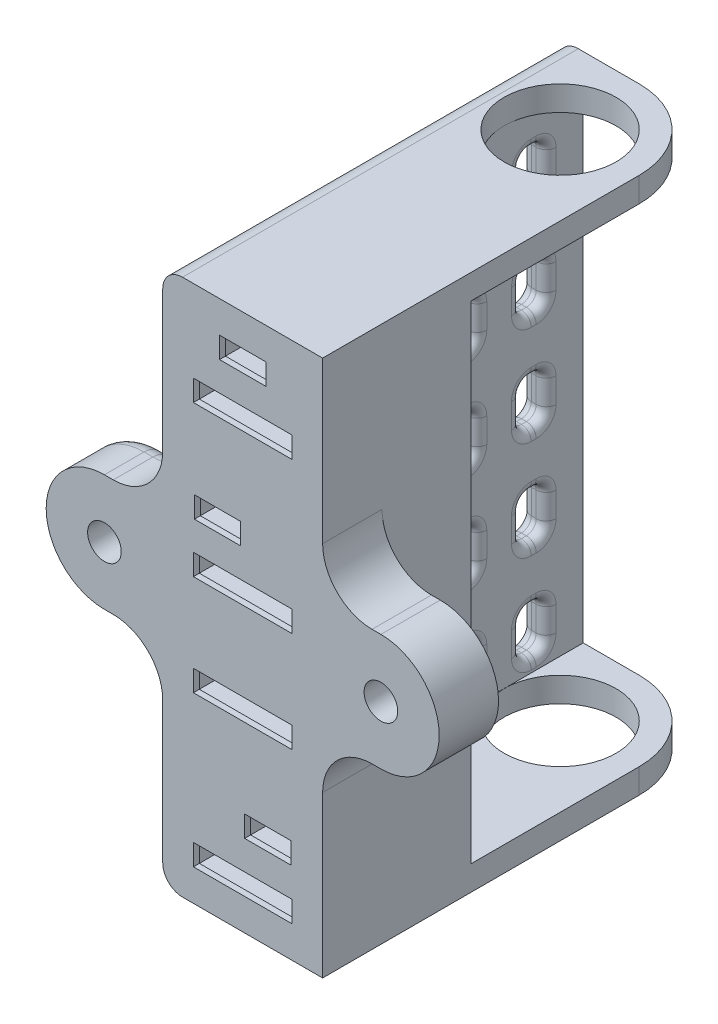
SolidWorks part; units mm, degrees
ref_plane "Plan de face" through (0, 0, 0) normal (0, 0, 1) x (1, 0, 0)
ref_plane "Plan de dessus" through (0, 0, 0) normal (0, 1, 0) x (1, 0, 0)
ref_plane "Plan de droite" through (0, 0, 0) normal (1, 0, 0) x (0, 0, -1)
sketch "Esquisse1" plane through (0, 0, 0) normal (0, 0, 1) x (1, 0, 0)
  line L44 (-8.08, 27.13) -> (8.08, 27.13)
  line L45 (-8.08, 27.13) -> (-8.08, -27.13)
  line L46 (-8.08, -27.13) -> (8.08, -27.13)
  line L47 (8.08, 27.13) -> (8.08, -27.13)
  line L48 (-8.08, 27.13) -> (8.08, -27.13) construction
  line L49 (-8.08, -27.13) -> (8.08, 27.13) construction
  point P1 (0, 0)
  dimension "D1" = 16.16
  dimension "D2" = 54.26
extrude "Boss.-Extru.1" add sketch "Esquisse1" along normal blind 15
sketch "Esquisse2" plane through (0, 0, 0) normal (0, 0, -1) x (-1, 0, 0)
  line L0 (8.08, -27.13) -> (-8.08, -27.13) construction
  line L1 (-2.54, 21.59) -> (2.54, 21.59) construction
  line L2 (-2.54, 21.59) -> (-2.54, 24.13) construction
  line L3 (-2.54, 24.13) -> (2.54, 24.13) construction
  line L4 (2.54, 21.59) -> (2.54, 24.13) construction
  line L5 (-2.54, 21.59) -> (2.54, 24.13) construction
  line L6 (-2.54, 24.13) -> (2.54, 21.59) construction
  line L7 (-5.08, 19.05) -> (5.08, 19.05) construction
  line L8 (-5.08, 19.05) -> (-5.08, 16.51) construction
  line L9 (-5.08, 16.51) -> (5.08, 16.51) construction
  line L10 (5.08, 19.05) -> (5.08, 16.51) construction
  line L11 (-5.08, 19.05) -> (5.08, 16.51) construction
  line L12 (-5.08, 16.51) -> (5.08, 19.05) construction
  line L13 (0, 24.13) -> (0, -24.13) construction
  line L14 (5.08, 6.35) -> (0, 6.35) construction
  line L15 (5.08, 6.35) -> (5.08, 8.89) construction
  line L16 (5.08, 8.89) -> (0, 8.89) construction
  line L17 (0, 6.35) -> (0, 8.89) construction
  line L18 (5.08, 6.35) -> (0, 8.89) construction
  line L19 (5.08, 8.89) -> (0, 6.35) construction
  line L21 (2.64, 24.23) -> (-2.64, 24.23)
  line L22 (5.08, 1.27) -> (-5.08, 1.27) construction
  line L23 (5.08, 1.27) -> (5.08, 3.81) construction
  line L24 (5.08, 3.81) -> (-5.08, 3.81) construction
  line L25 (-5.08, 1.27) -> (-5.08, 3.81) construction
  line L26 (5.08, 1.27) -> (-5.08, 3.81) construction
  line L27 (5.08, 3.81) -> (-5.08, 1.27) construction
  line L28 (2.64, 24.23) -> (2.64, 21.49)
  line L29 (-5.08, -8.89) -> (5.08, -8.89) construction
  line L30 (-5.08, -8.89) -> (-5.08, -6.35) construction
  line L31 (-5.08, -6.35) -> (5.08, -6.35) construction
  line L32 (5.08, -8.89) -> (5.08, -6.35) construction
  line L33 (-5.08, -8.89) -> (5.08, -6.35) construction
  line L34 (-5.08, -6.35) -> (5.08, -8.89) construction
  line L35 (2.64, 21.49) -> (-2.64, 21.49)
  line L36 (0, -16.51) -> (-5.08, -16.51) construction
  line L37 (0, -16.51) -> (0, -19.05) construction
  line L38 (0, -19.05) -> (-5.08, -19.05) construction
  line L39 (-5.08, -16.51) -> (-5.08, -19.05) construction
  line L40 (0, -16.51) -> (-5.08, -19.05) construction
  line L41 (0, -19.05) -> (-5.08, -16.51) construction
  line L42 (-2.64, 24.23) -> (-2.64, 21.49)
  line L43 (2.64, 24.23) -> (-2.64, 21.49) construction
  line L44 (5.08, -24.13) -> (-5.08, -24.13) construction
  line L45 (5.08, -24.13) -> (5.08, -21.59) construction
  line L46 (5.08, -21.59) -> (-5.08, -21.59) construction
  line L47 (-5.08, -24.13) -> (-5.08, -21.59) construction
  line L48 (5.08, -24.13) -> (-5.08, -21.59) construction
  line L49 (5.08, -21.59) -> (-5.08, -24.13) construction
  line L50 (2.64, 21.49) -> (-2.64, 24.23) construction
  line L51 (5.28, 19.15) -> (-5.28, 19.15)
  line L52 (5.28, 19.15) -> (5.28, 16.41)
  line L53 (5.28, 16.41) -> (-5.28, 16.41)
  line L54 (-5.28, 19.15) -> (-5.28, 16.41)
  line L55 (5.28, 19.15) -> (-5.28, 16.41) construction
  line L56 (5.28, 16.41) -> (-5.28, 19.15) construction
  line L57 (5.18, 8.99) -> (-0.1, 8.99)
  line L58 (5.18, 8.99) -> (5.18, 6.25)
  line L59 (5.18, 6.25) -> (-0.1, 6.25)
  line L60 (-0.1, 8.99) -> (-0.1, 6.25)
  line L61 (5.18, 8.99) -> (-0.1, 6.25) construction
  line L62 (5.18, 6.25) -> (-0.1, 8.99) construction
  line L63 (5.28, 3.91) -> (-5.28, 3.91)
  line L64 (5.28, 3.91) -> (5.28, 1.17)
  line L65 (5.28, 1.17) -> (-5.28, 1.17)
  line L66 (-5.28, 3.91) -> (-5.28, 1.17)
  line L67 (5.28, 3.91) -> (-5.28, 1.17) construction
  line L68 (5.28, 1.17) -> (-5.28, 3.91) construction
  line L69 (5.28, -6.25) -> (-5.28, -6.25)
  line L70 (5.28, -6.25) -> (5.28, -8.99)
  line L71 (5.28, -8.99) -> (-5.28, -8.99)
  line L72 (-5.28, -6.25) -> (-5.28, -8.99)
  line L73 (5.28, -6.25) -> (-5.28, -8.99) construction
  line L74 (5.28, -8.99) -> (-5.28, -6.25) construction
  line L75 (0.1, -16.41) -> (-5.18, -16.41)
  line L76 (0.1, -16.41) -> (0.1, -19.15)
  line L77 (0.1, -19.15) -> (-5.18, -19.15)
  line L78 (-5.18, -16.41) -> (-5.18, -19.15)
  line L79 (0.1, -16.41) -> (-5.18, -19.15) construction
  line L80 (0.1, -19.15) -> (-5.18, -16.41) construction
  line L81 (5.28, -21.49) -> (-5.28, -21.49)
  line L82 (5.28, -21.49) -> (5.28, -24.23)
  line L83 (5.28, -24.23) -> (-5.28, -24.23)
  line L84 (-5.28, -21.49) -> (-5.28, -24.23)
  line L85 (5.28, -21.49) -> (-5.28, -24.23) construction
  line L86 (5.28, -24.23) -> (-5.28, -21.49) construction
  point P4 (0, 22.86)
  point P5 (0, -24.13)
  point P11 (0, 17.78)
  point P12 (0, 17.78)
  point P14 (0, -27.13)
  point P19 (2.54, 7.62)
  point P20 (0, 0)
  point P24 (0, 22.86)
  point P29 (0, 2.54)
  point P37 (0, -7.62)
  point P45 (-2.54, -17.78)
  point P47 (2.54, 7.62)
  point P54 (0, -22.86)
  point P57 (0, 2.54)
  point P62 (0, -7.62)
  point P68 (-2.54, -17.78)
  point P73 (0, -22.86)
  dimension "D1" = 5.08
  dimension "D2" = 5.08
  dimension "D3" = 5.08
  dimension "D4" = 10.16
  dimension "D5" = 10.16
  dimension "D6" = 10.16
  dimension "D7" = 2.54
  dimension "D8" = 10.16
  dimension "D9" = 5.08
  dimension "D10" = 0.2
  dimension "D11" = 0.1
  dimension "D12" = 0.1
extrude "Enlèv. mat.-Extru.1" cut sketch "Esquisse2" against normal through all
sketch "Esquisse4" plane through (0, 0, 15) normal (0, 0, 1) x (1, 0, 0)
  line L0 (-4.98, -21.79) -> (-4.98, -23.93)
  line L1 (-4.98, -23.93) -> (4.98, -23.93)
  line L2 (4.98, -23.93) -> (4.98, -21.79)
  line L3 (4.98, -21.79) -> (-4.98, -21.79)
  line L4 (5.28, 16.41) -> (5.28, 19.15)
  line L5 (-5.28, 16.41) -> (5.28, 16.41)
  line L6 (-5.28, 19.15) -> (-5.28, 16.41)
  line L7 (5.28, 19.15) -> (-5.28, 19.15)
  line L8 (5.28, 16.41) -> (5.28, 19.15)
  line L9 (-5.28, 16.41) -> (5.28, 16.41)
  line L10 (-5.28, 19.15) -> (-5.28, 16.41)
  line L11 (5.28, 19.15) -> (-5.28, 19.15)
  line L12 (2.64, 21.49) -> (2.64, 24.23)
  line L13 (-2.64, 21.49) -> (2.64, 21.49)
  line L14 (-2.64, 24.23) -> (-2.64, 21.49)
  line L15 (2.64, 24.23) -> (-2.64, 24.23)
  line L16 (2.64, 21.49) -> (2.64, 24.23)
  line L17 (-2.64, 21.49) -> (2.64, 21.49)
  line L18 (-2.64, 24.23) -> (-2.64, 21.49)
  line L19 (2.64, 24.23) -> (-2.64, 24.23)
  line L20 (0.1, 6.25) -> (0.1, 8.99)
  line L21 (-5.18, 6.25) -> (0.1, 6.25)
  line L22 (-5.18, 8.99) -> (-5.18, 6.25)
  line L23 (0.1, 8.99) -> (-5.18, 8.99)
  line L24 (0.1, 6.25) -> (0.1, 8.99)
  line L25 (-5.18, 6.25) -> (0.1, 6.25)
  line L26 (-5.18, 8.99) -> (-5.18, 6.25)
  line L27 (0.1, 8.99) -> (-5.18, 8.99)
  line L28 (5.28, 1.17) -> (5.28, 3.91)
  line L29 (-5.28, 1.17) -> (5.28, 1.17)
  line L30 (-5.28, 3.91) -> (-5.28, 1.17)
  line L31 (5.28, 3.91) -> (-5.28, 3.91)
  line L32 (5.28, 1.17) -> (5.28, 3.91)
  line L33 (-5.28, 1.17) -> (5.28, 1.17)
  line L34 (-5.28, 3.91) -> (-5.28, 1.17)
  line L35 (5.28, 3.91) -> (-5.28, 3.91)
  line L36 (5.28, -8.99) -> (5.28, -6.25)
  line L37 (-5.28, -8.99) -> (5.28, -8.99)
  line L38 (-5.28, -6.25) -> (-5.28, -8.99)
  line L39 (5.28, -6.25) -> (-5.28, -6.25)
  line L40 (5.28, -8.99) -> (5.28, -6.25)
  line L41 (-5.28, -8.99) -> (5.28, -8.99)
  line L42 (-5.28, -6.25) -> (-5.28, -8.99)
  line L43 (5.28, -6.25) -> (-5.28, -6.25)
  line L44 (5.18, -19.15) -> (5.18, -16.41)
  line L45 (-0.1, -19.15) -> (5.18, -19.15)
  line L46 (-0.1, -16.41) -> (-0.1, -19.15)
  line L47 (5.18, -16.41) -> (-0.1, -16.41)
  line L48 (5.18, -19.15) -> (5.18, -16.41)
  line L49 (-0.1, -19.15) -> (5.18, -19.15)
  line L50 (-0.1, -16.41) -> (-0.1, -19.15)
  line L51 (5.18, -16.41) -> (-0.1, -16.41)
  line L52 (5.28, -24.23) -> (5.28, -21.49)
  line L53 (-5.28, -24.23) -> (5.28, -24.23)
  line L54 (-5.28, -21.49) -> (-5.28, -24.23)
  line L55 (5.28, -21.49) -> (-5.28, -21.49)
  line L56 (5.28, -24.23) -> (5.28, -21.49)
  line L57 (-5.28, -24.23) -> (5.28, -24.23)
  line L58 (-5.28, -21.49) -> (-5.28, -24.23)
  line L59 (5.28, -21.49) -> (-5.28, -21.49)
  line L60 (0.2, -16.71) -> (0.2, -18.85)
  line L61 (0.2, -18.85) -> (4.88, -18.85)
  line L62 (4.88, -18.85) -> (4.88, -16.71)
  line L63 (4.88, -16.71) -> (0.2, -16.71)
  line L64 (-4.98, -6.55) -> (-4.98, -8.69)
  line L65 (-4.98, -8.69) -> (4.98, -8.69)
  line L66 (4.98, -8.69) -> (4.98, -6.55)
  line L67 (4.98, -6.55) -> (-4.98, -6.55)
  line L68 (-4.98, 3.61) -> (-4.98, 1.47)
  line L69 (-4.98, 1.47) -> (4.98, 1.47)
  line L70 (4.98, 1.47) -> (4.98, 3.61)
  line L71 (4.98, 3.61) -> (-4.98, 3.61)
  line L72 (-4.88, 8.69) -> (-4.88, 6.55)
  line L73 (-4.88, 6.55) -> (-0.2, 6.55)
  line L74 (-0.2, 6.55) -> (-0.2, 8.69)
  line L75 (-0.2, 8.69) -> (-4.88, 8.69)
  line L76 (-4.98, 18.85) -> (-4.98, 16.71)
  line L77 (-4.98, 16.71) -> (4.98, 16.71)
  line L78 (4.98, 16.71) -> (4.98, 18.85)
  line L79 (4.98, 18.85) -> (-4.98, 18.85)
  line L80 (-2.34, 23.93) -> (-2.34, 21.79)
  line L81 (-2.34, 21.79) -> (2.34, 21.79)
  line L82 (2.34, 21.79) -> (2.34, 23.93)
  line L83 (2.34, 23.93) -> (-2.34, 23.93)
  dimension "D1" = 0
  dimension "D2" = 0
  dimension "D3" = 0
  dimension "D4" = 0
  dimension "D5" = 0
  dimension "D6" = 0
  dimension "D7" = 0
  dimension "D8" = 0.3
extrude "Boss.-Extru.2" add sketch "Esquisse4" against normal blind 0.6
sketch "Esquisse5" plane through (0, 0, 0) normal (0, 0, -1) x (-1, 0, 0)
  line L0 (8.08, -27.13) -> (-8.08, -27.13) construction
  line L1 (8.08, 27.13) -> (5.58, 27.13)
  line L2 (8.08, 27.13) -> (8.08, -27.13)
  line L3 (8.08, -27.13) -> (5.58, -27.13)
  line L4 (5.58, 27.13) -> (5.58, -27.13)
  line L5 (8.08, 27.13) -> (5.58, -27.13) construction
  line L6 (8.08, -27.13) -> (5.58, 27.13) construction
  point P4 (6.83, 0)
  dimension "D1" = 2.5
extrude "Boss.-Extru.3" add sketch "Esquisse5" along normal blind 25
sketch "Esquisse7" plane through (-5.58, 0, 0) normal (1, 0, 0) x (0, 0, -1)
  line L0 (20, -21.13) -> (13, -21.13) construction
  line L1 (21.25, -23.38) -> (18.75, -23.38)
  line L2 (21.25, -23.38) -> (21.25, -18.88)
  line L3 (21.25, -18.88) -> (18.75, -18.88)
  line L4 (18.75, -23.38) -> (18.75, -18.88)
  line L5 (21.25, -23.38) -> (18.75, -18.88) construction
  line L6 (21.25, -18.88) -> (18.75, -23.38) construction
  line L7 (14.25, -23.38) -> (11.75, -23.38)
  line L8 (14.25, -23.38) -> (14.25, -18.88)
  line L9 (14.25, -18.88) -> (11.75, -18.88)
  line L10 (11.75, -23.38) -> (11.75, -18.88)
  line L11 (14.25, -23.38) -> (11.75, -18.88) construction
  line L12 (14.25, -18.88) -> (11.75, -23.38) construction
  line L13 (25, -27.13) -> (0, -27.13) construction
  line L14 (25, 27.13) -> (25, -27.13) construction
  point P4 (20, -21.13)
  point P9 (13, -21.13)
  dimension "D1" = 7
  dimension "D2" = 2.5
  dimension "D3" = 4.5
  dimension "D4" = 6
  dimension "D5" = 5
extrude "Enlèv. mat.-Extru.3" cut sketch "Esquisse7" against normal through all
pattern_linear "Répétition linéaire1" count 5 spacing 10 along (0, 1, 0) of "Enlèv. mat.-Extru.3"
fillet "Congé2" radius 1 120 edges at (-8.08, -18.88, -20) (-5.58, -18.88, -20) (-8.08, -23.38, -20) (-5.58, -23.38, -20) (-8.08, -8.88, -20) (-5.58, -8.88, -20) (-8.08, -13.38, -20) (-5.58, -13.38, -20) (-8.08, 1.12, -20) (-5.58, 1.12, -20) (-8.08, -3.38, -20) (-5.58, -3.38, -20) (-8.08, 11.12, -20) (-5.58, 11.12, -20) (-8.08, 6.62, -20) (-5.58, 6.62, -20) (-8.08, 21.12, -20) (-5.58, 21.12, -20) (-8.08, 16.62, -20) (-5.58, 16.62, -20) (-8.08, 21.12, -13) (-5.58, 21.12, -13) (-8.08, 16.62, -13) (-5.58, 16.62, -13) (-8.08, 11.12, -13) (-5.58, 11.12, -13) (-8.08, 6.62, -13) (-5.58, 6.62, -13) (-8.08, 1.12, -13) (-5.58, 1.12, -13) (-8.08, -3.38, -13) (-5.58, -3.38, -13) (-8.08, -8.88, -13) (-5.58, -8.88, -13) (-8.08, -13.38, -13) (-5.58, -13.38, -13) (-8.08, -18.88, -13) (-5.58, -18.88, -13) (-8.08, -23.38, -13) (-5.58, -23.38, -13) (-8.08, -21.13, -14.25) (-5.58, -21.13, -14.25) (-8.08, -11.13, -14.25) (-5.58, -11.13, -14.25) (-8.08, -1.13, -14.25) (-5.58, -1.13, -14.25) (-8.08, 8.87, -14.25) (-5.58, 8.87, -14.25) (-8.08, 18.87, -14.25) (-5.58, 18.87, -14.25) (-8.08, 18.87, -21.25) (-5.58, 18.87, -21.25) (-8.08, 8.87, -21.25) (-5.58, 8.87, -21.25) (-8.08, -1.13, -21.25) (-5.58, -1.13, -21.25) (-8.08, -11.13, -21.25) (-5.58, -11.13, -21.25) (-8.08, -21.13, -21.25) (-5.58, -21.13, -21.25) (-8.08, -21.13, -18.75) (-5.58, -21.13, -18.75) (-8.08, -11.13, -18.75) (-5.58, -11.13, -18.75) (-8.08, -1.13, -18.75) (-5.58, -1.13, -18.75) (-8.08, 8.87, -18.75) (-5.58, 8.87, -18.75) (-8.08, 18.87, -18.75) (-5.58, 18.87, -18.75) (-8.08, 18.87, -11.75) (-5.58, 18.87, -11.75) (-8.08, 8.87, -11.75) (-5.58, 8.87, -11.75) (-8.08, -1.13, -11.75) (-5.58, -1.13, -11.75) (-8.08, -11.13, -11.75) (-5.58, -11.13, -11.75) (-8.08, -21.13, -11.75) (-5.58, -21.13, -11.75) (-6.83, -23.38, -14.25) (-6.83, -18.88, -14.25) (-6.83, -13.38, -14.25) (-6.83, -8.88, -14.25) (-6.83, -3.38, -14.25) (-6.83, 1.12, -14.25) (-6.83, 6.62, -14.25) (-6.83, 11.12, -14.25) (-6.83, 16.62, -14.25) (-6.83, 21.12, -14.25) (-6.83, 16.62, -21.25) (-6.83, 21.12, -21.25) (-6.83, 6.62, -21.25) (-6.83, 11.12, -21.25) (-6.83, -3.38, -21.25) (-6.83, 1.12, -21.25) (-6.83, -13.38, -21.25) (-6.83, -8.88, -21.25) (-6.83, -23.38, -21.25) (-6.83, -18.88, -21.25) (-6.83, -18.88, -18.75) (-6.83, -23.38, -18.75) (-6.83, -8.88, -18.75) (-6.83, -13.38, -18.75) (-6.83, 1.12, -18.75) (-6.83, -3.38, -18.75) (-6.83, 11.12, -18.75) (-6.83, 6.62, -18.75) (-6.83, 21.12, -18.75) (-6.83, 16.62, -18.75) (-6.83, 21.12, -11.75) (-6.83, 16.62, -11.75) (-6.83, 11.12, -11.75) (-6.83, 6.62, -11.75) (-6.83, 1.12, -11.75) (-6.83, -3.38, -11.75) (-6.83, -8.88, -11.75) (-6.83, -13.38, -11.75) (-6.83, -18.88, -11.75) (-6.83, -23.38, -11.75)
sketch "Esquisse11" plane through (0, -27.13, 0) normal (0, -1, 0) x (1, 0, 0)
  line L0 (8.08, 0) -> (8.08, -25)
  line L1 (-5.58, -25) -> (8.08, -25)
  line L2 (-5.58, -25) -> (-5.58, 0)
  line L3 (-5.58, 0) -> (8.08, 0)
extrude "Boss.-Extru.6" add sketch "Esquisse11" against normal blind 2.5
fillet "Congé4" radius 8 1 edges at (8.08, -25.88, -25)
sketch "Esquisse12" plane through (0, -24.63, 0) normal (0, 1, 0) x (1, 0, 0)
  line L0 (-5.58, 0) -> (-5.58, 25) construction
  circle A0 centre (0.08, 17) radius 5.66
  arc A1 (8.08, 17) -> (0.08, 25) centre (0.08, 17) ccw construction
extrude "Enlèv. mat.-Extru.4" cut sketch "Esquisse12" against normal through all
mirror "Symétrie1" about plane through (0, 0, 0) normal (0, 1, 0) of "Enlèv. mat.-Extru.4", "Boss.-Extru.6", "Congé4"
sketch "Esquisse13" plane through (0, 0, 15) normal (0, 0, 1) x (1, 0, 0)
  line L0 (13.97, 5.89) -> (8.08, 5.89)
  line L1 (8.08, -27.13) -> (8.08, 27.13) construction
  line L2 (-8.08, 5.89) -> (-13.97, 5.89)
  line L3 (-8.08, 5.89) -> (-8.08, -5.89)
  line L4 (-13.97, -5.89) -> (-8.08, -5.89)
  line L5 (8.08, 5.89) -> (8.08, -27.13)
  line L6 (8.08, -5.89) -> (13.97, -5.89)
  line L7 (-8.08, 27.13) -> (-8.08, -27.13) construction
  arc A0 (-13.97, 5.89) -> (-13.97, -5.89) centre (-13.97, 0) ccw
  arc A1 (13.97, -5.89) -> (13.97, 5.89) centre (13.97, 0) ccw
  line M3 (-8.08, 27.13) -> (-8.08, -27.13)
  dimension "D1" = 11.78
  dimension "D2" = 13.97
  dimension "D3" = 13.97
extrude "Boss.-Extru.7" add sketch "Esquisse13" against normal blind 6 contours L6 A1 L0 L5 | L2 A0 L4 M3 region at (13.4202, 0, 15) region at (-13.4202, 0, 15)
hole_wizard "Chambrage pour vis à tête ronde bombée M31" positions "Esquisse14" profile "Esquisse16" counterbore size "M3" standard "Ansi Metric" end condition through all
sketch "Esquisse14" plane through (0, 0, 9) normal (0, 0, -1) x (-1, 0, 0)
  point P0 (-13.97, 0)
  point P3 (13.97, 0)
sketch "Esquisse16" plane through (13.97, 0, 9) normal (1, 0, 0) x (0, 1, 0)
  line L0 (0, 0) -> (0, 6)
  line L1 (0, 6) -> (1.7, 6)
  line L3 (1.7, 6) -> (1.7, 2.4)
  line L4 (1.7, 2.4) -> (3.5, 2.4)
  line L5 (3.5, 2.4) -> (3.5, 0)
  line L7 (3.5, 0) -> (0, 0)
  line L11 (0, -6.35) -> (0, 107.95) construction
  dimension "Diamètre du perçage jusqu'au prochain" = 3.4
  dimension "Profondeur du perçage jusqu'au prochain" = 6
  dimension "Diamètre du chambrage" = 7
  dimension "Profondeur du chambrage" = 2.4
fillet "Congé5" radius 5 4 edges at (-8.08, 5.89, 12) (-8.08, -5.89, 12) (8.08, -5.89, 12) (8.08, 5.89, 12)
fillet "Congé6" radius 2 2 edges at (-8.08, -27.13, -5) (-8.08, 27.13, -5)
fillet "Congé7" radius 2 5 edges at (-9.5445, -7.3545, 9) (-13.525, -5.89, 9) (-19.86, 0, 9) (-13.525, 5.89, 9) (-9.5445, 7.3545, 9)
equation "\"PressFit Offset\"= 0.1mm"
equation "\"D10@Esquisse2\"=\"PressFit Offset\"*2"
equation "\"D11@Esquisse2\"=\"PressFit Offset\""
equation "\"D12@Esquisse2\"=\"PressFit Offset\""
